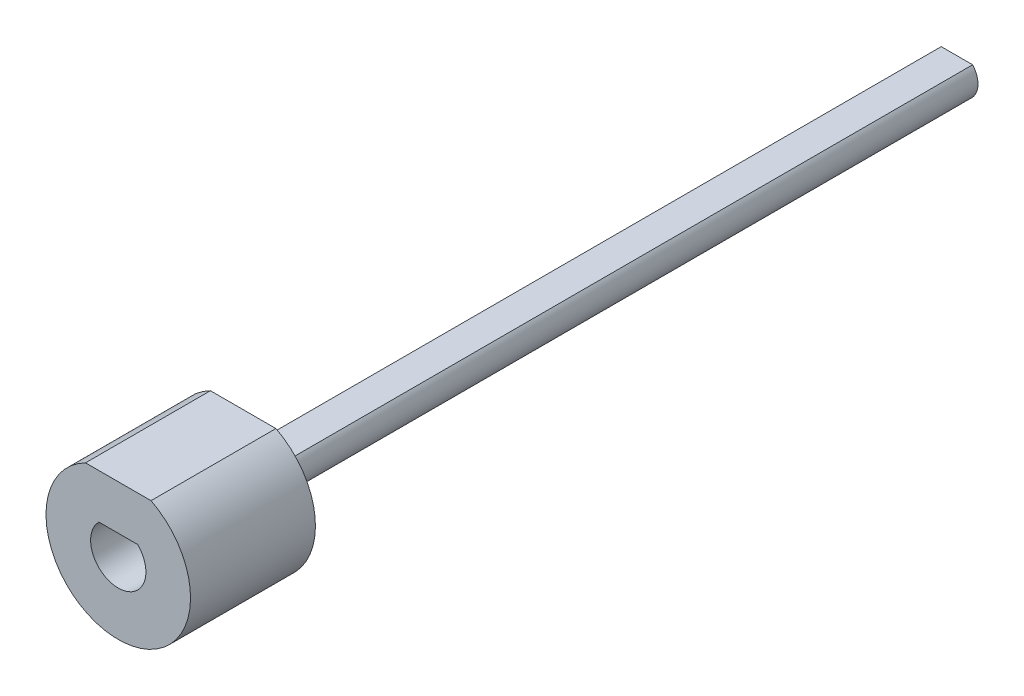
SolidWorks part; units mm, degrees
ref_plane "Front Plane" through (0, 0, 0) normal (0, 0, 1) x (1, 0, 0)
ref_plane "Top Plane" through (0, 0, 0) normal (0, 1, 0) x (1, 0, 0)
ref_plane "Right Plane" through (0, 0, 0) normal (1, 0, 0) x (0, 0, -1)
sketch "Sketch1" plane through (0, 0, 0) normal (0, 0, 1) x (1, 0, 0)
  line L0 (0, -1.9685) -> (0, 1.4097) construction
  line L1 (-1.3739, 1.4097) -> (1.3739, 1.4097)
  line L2 (-2.3315, 4.5847) -> (2.3315, 4.5847)
  arc A0 (-1.3739, 1.4097) -> (1.3739, 1.4097) centre (0, 0) ccw
  arc A1 (-2.3315, 4.5847) -> (2.3315, 4.5847) centre (0, 0) ccw
  dimension "D1" = 3.937
  dimension "D2" = 3.3782
  dimension "D3" = 3.175
extrude "Boss-Extrude1" add sketch "Sketch1" along normal blind 6.35
sketch "Sketch3" plane through (0, 0, 0) normal (0, 0, -1) x (-1, 0, 0)
  line L0 (-2.3315, 4.5847) -> (2.3315, 4.5847) construction
  line L1 (-2.3315, 4.5847) -> (2.3315, 4.5847)
  arc A0 (-2.3315, 4.5847) -> (2.3315, 4.5847) centre (0, 0) ccw construction
  arc A1 (-2.3315, 4.5847) -> (2.3315, 4.5847) centre (0, 0) ccw
extrude "Boss-Extrude2" add sketch "Sketch3" along normal blind 2.54
sketch "Sketch2" plane through (0, 0, -2.54) normal (0, 0, -1) x (-1, 0, 0)
  line L0 (1.118, 1) -> (-1.118, 1) construction
  line L1 (1.118, 1) -> (-1.118, 1)
  arc A0 (-1.118, 1) -> (1.118, 1) centre (0, 0) ccw construction
  arc A1 (-1.118, 1) -> (1.118, 1) centre (0, 0) ccw
extrude "Boss-Extrude3" add sketch "Sketch2" along normal blind 50.8
